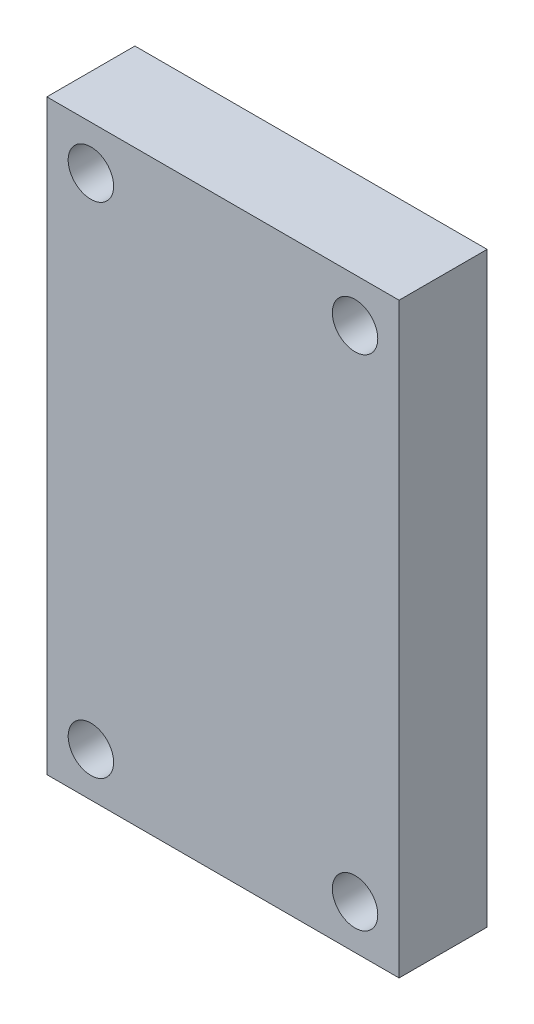
SolidWorks part; units mm, degrees
material "PE High Density"
ref_plane "Front Plane" through (0, 0, 0) normal (0, 0, 1) x (1, 0, 0)
ref_plane "Top Plane" through (0, 0, 0) normal (0, 1, 0) x (1, 0, 0)
ref_plane "Right Plane" through (0, 0, 0) normal (1, 0, 0) x (0, 0, -1)
sketch "Sketch1" plane through (0, 0, 0) normal (0, 0, 1) x (1, 0, 0)
  line L0 (0, 0) -> (0, 63.5)
  line L1 (0, 63.5) -> (38.1, 63.5)
  line L2 (38.1, 63.5) -> (38.1, 0)
  line L3 (38.1, 0) -> (0, 0)
  dimension "D1" = 63.5
  dimension "D2" = 38.1
extrude "Boss-Extrude1" add sketch "Sketch1" along normal blind 9.525
sketch "Sketch5" plane through (0, 0, 9.525) normal (0, 0, 1) x (1, 0, 0)
  line L0 (0, 58.7375) -> (38.1, 58.7375) construction
  line L1 (0, 63.5) -> (0, 0) construction
  line L2 (38.1, 0) -> (38.1, 63.5) construction
  line L3 (38.1, 63.5) -> (0, 63.5) construction
  line L4 (0, 31.75) -> (38.1, 31.75) construction
  line L5 (0, 4.7625) -> (38.1, 4.7625) construction
  line L6 (19.05, 63.5) -> (19.05, 0) construction
  line L7 (0, 0) -> (38.1, 0) construction
  line L8 (4.7625, 63.5) -> (4.7625, 0) construction
  line L9 (33.3375, 63.5) -> (33.3375, 0) construction
  point P20 (4.7625, 58.7375)
  point P21 (19.05, 58.7375)
  point P22 (33.3375, 58.7375)
  point P23 (33.3375, 31.75)
  point P24 (4.7625, 31.75)
  dimension "D1" = 4.7625
  dimension "D2" = 4.7625
hole_wizard "#10 (0.1935) Diameter Hole1" positions "Sketch7" profile "Sketch6" hole size "#10" standard "ANSI Inch" end condition through all
sketch "Sketch7" plane through (0, 0, 9.525) normal (0, 0, 1) x (1, 0, 0)
  line L0 (0, 4.7625) -> (38.1, 4.7625) construction
  line L1 (4.7625, 63.5) -> (4.7625, 0) construction
  line L2 (33.3375, 63.5) -> (33.3375, 0) construction
  point P0 (4.7625, 58.7375)
  point P3 (33.3375, 58.7375)
  point P6 (4.7625, 4.7625)
  point P12 (33.3375, 4.7625)
sketch "Sketch6" plane through (4.7625, 58.7375, 9.525) normal (1, 0, 0) x (0, -1, 0)
  line L0 (0, 0) -> (0, 9.525)
  line L1 (0, 9.525) -> (2.4574, 9.525)
  line L2 (2.4574, 9.525) -> (2.4574, 0)
  line L5 (2.4574, 0) -> (0, 0)
  line L11 (0, -6.35) -> (0, 107.95) construction
  dimension "Thru Hole Dia." = 4.9149
  dimension "Thru Hole Depth" = 9.525
